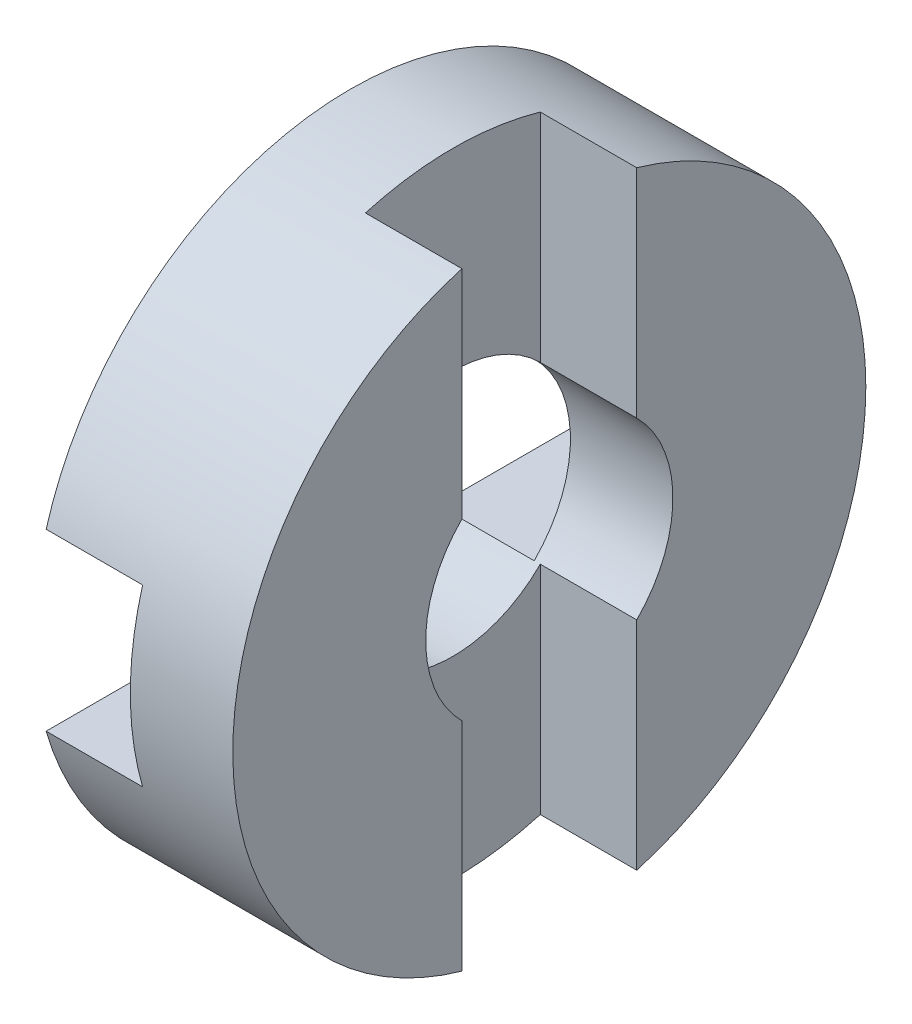
SolidWorks part; units mm, degrees
ref_plane "Front Plane" through (0, 0, 0) normal (0, 0, 1) x (1, 0, 0)
ref_plane "Top Plane" through (0, 0, 0) normal (0, 1, 0) x (1, 0, 0)
ref_plane "Right Plane" through (0, 0, 0) normal (1, 0, 0) x (0, 0, -1)
ref_plane "Plane1" through (0, 0, 0) normal (0, 0, 1) x (1, 0, 0)
sketch "Sketch1" plane through (0, 0, 0) normal (0, 0, 1) x (1, 0, 0)
  line L0 (0, 10.5) -> (0, 4.1)
  line L1 (0, 4.1) -> (6.6, 4.1)
  line L2 (6.6, 4.1) -> (6.6, 10.5)
  line L3 (6.6, 10.5) -> (0, 10.5)
  line L4 (6.6, 0) -> (0, 0) construction
revolve "Revolve1" add sketch "Sketch1" angle 360 about L4 reverse direction yes
ref_plane "Plane2" through (0, 0, 0) normal (0, 0, 1) x (1, 0, 0)
sketch "Sketch2" plane through (0, 0, 0) normal (0, 0, 1) x (1, 0, 0)
  line L0 (0, -2.9) -> (3.2, -2.9)
  line L1 (3.2, -2.9) -> (3.2, 2.9)
  line L2 (3.2, 2.9) -> (0, 2.9)
  line L3 (0, 2.9) -> (0, -2.9)
extrude "Cut-Extrude1" cut sketch "Sketch2" against normal blind 10.5 and the other way blind 10.5
ref_plane "Plane3" through (0, 0, 0) normal (0, 1, 0) x (-1, 0, 0)
sketch "Sketch3" plane through (0, 0, 0) normal (0, 1, 0) x (-1, 0, 0)
  line L0 (-3.4, -2.9) -> (-3.4, 2.9)
  line L1 (-3.4, 2.9) -> (-6.6, 2.9)
  line L2 (-6.6, 2.9) -> (-6.6, -2.9)
  line L3 (-6.6, -2.9) -> (-3.4, -2.9)
extrude "Cut-Extrude2" cut sketch "Sketch3" against normal blind 10.5 and the other way blind 10.5
